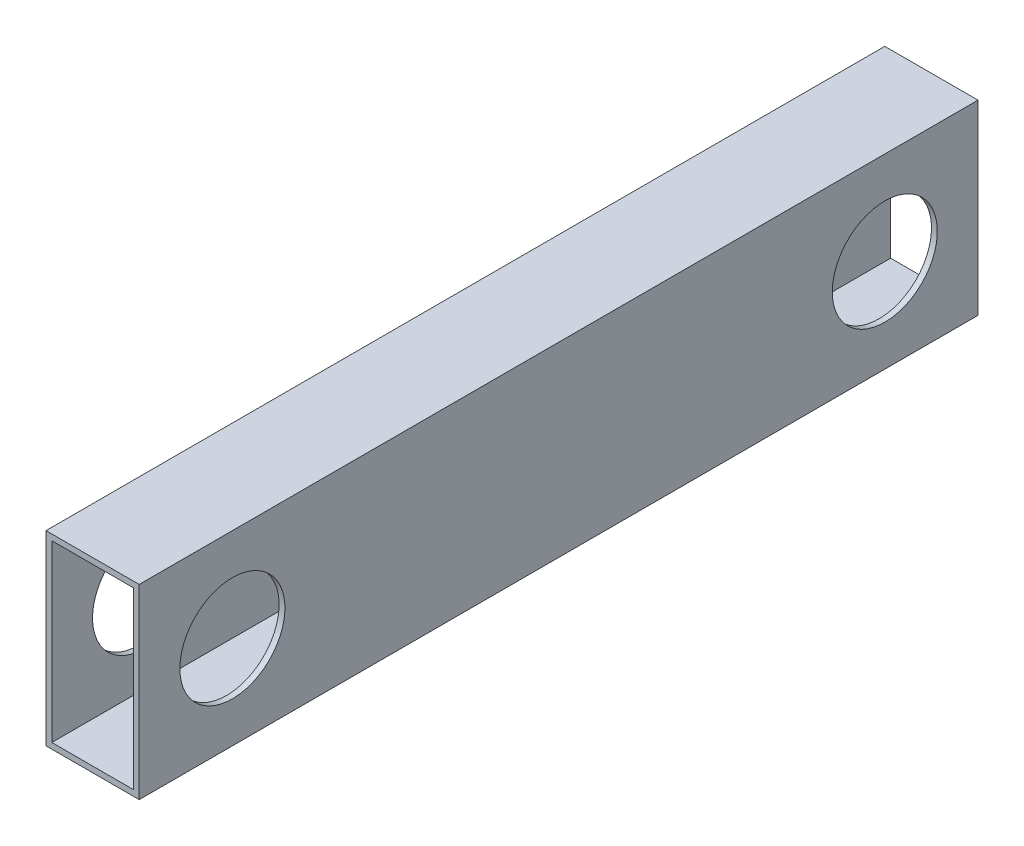
SolidWorks part; units mm, degrees
ref_plane "Front Plane" through (0, 0, 0) normal (0, 0, 1) x (1, 0, 0)
ref_plane "Top Plane" through (0, 0, 0) normal (0, 1, 0) x (1, 0, 0)
ref_plane "Right Plane" through (0, 0, 0) normal (1, 0, 0) x (0, 0, -1)
sketch "Sketch1" plane through (0, 0, 0) normal (0, 0, 1) x (1, 0, 0)
  line L0 (0, 0) -> (25.4, 50.8) construction
  line L1 (0, 0) -> (25.4, 0)
  line L2 (0, 0) -> (0, 50.8)
  line L3 (0, 50.8) -> (25.4, 50.8)
  line L4 (25.4, 0) -> (25.4, 50.8)
  line L6 (1.5875, 49.2125) -> (23.8125, 49.2125)
  line L7 (1.5875, 49.2125) -> (1.5875, 1.5875)
  line L8 (1.5875, 1.5875) -> (23.8125, 1.5875)
  line L9 (23.8125, 49.2125) -> (23.8125, 1.5875)
  line L10 (1.5875, 49.2125) -> (23.8125, 1.5875) construction
  line L11 (1.5875, 1.5875) -> (23.8125, 49.2125) construction
  point P5 (12.7, 25.4)
  point P6 (12.7, 25.4)
  dimension "D1" = 25.4
  dimension "D2" = 50.8
  dimension "D3" = 1.5875
  dimension "D4" = 1.5875
extrude "Boss-Extrude1" add sketch "Sketch1" along normal blind 228.6
sketch "Sketch2" plane through (25.4, 0, 0) normal (1, 0, 0) x (0, 0, -1)
  line L0 (0, 0) -> (0, 50.8) construction
  line L1 (-228.6, 50.8) -> (0, 50.8) construction
  line L2 (-114.3, 50.8) -> (-114.3, 104.8222) construction
  circle A0 centre (-25.4, 25.4) radius 14.3129
  circle A1 centre (-203.2, 25.4) radius 14.3129
  point P10 (-114.3, 50.8)
  point P11 (0, 0)
  dimension "D1" = 25.4
  dimension "D3" = 28.6258
  dimension "D2" = 25.4
extrude "Cut-Extrude1" cut sketch "Sketch2" against normal through all both and the other way through all
ref_plane "Plane1" through (12.7, 0, 0) normal (1, 0, 0) x (0, 0, -1)
ref_plane "Plane2" through (0, 0, 114.3) normal (0, 0, 1) x (1, 0, 0)
